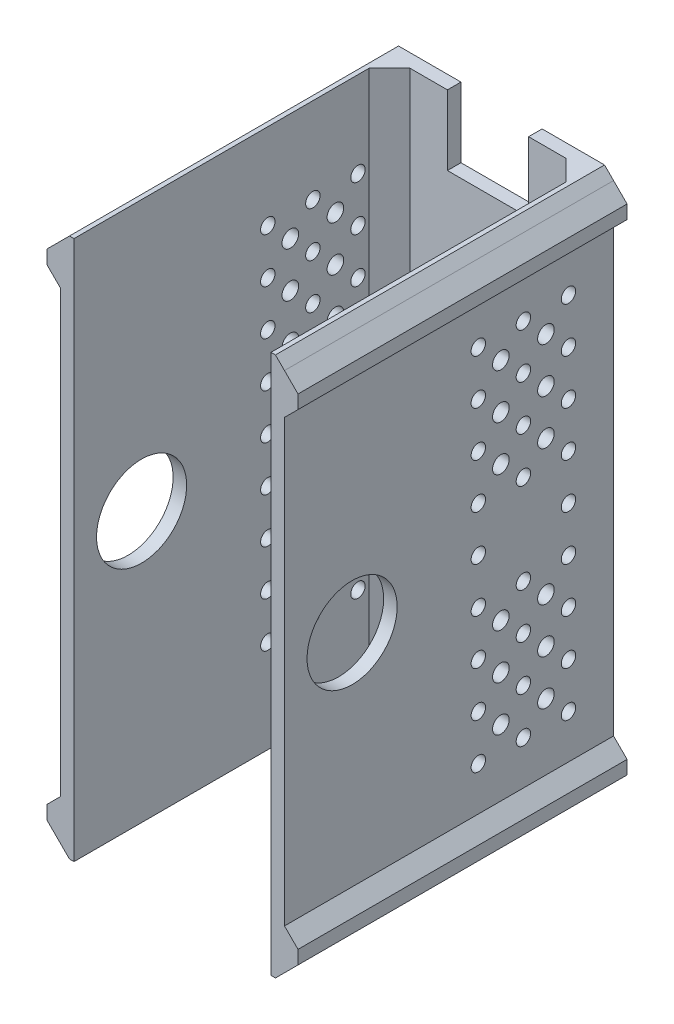
SolidWorks part; units mm, degrees
ref_plane "Front Plane" through (0, 0, 0) normal (0, 0, 1) x (1, 0, 0)
ref_plane "Top Plane" through (0, 0, 0) normal (0, 1, 0) x (1, 0, 0)
ref_plane "Right Plane" through (0, 0, 0) normal (1, 0, 0) x (0, 0, -1)
sketch "Sketch1" plane through (0, 0, 0) normal (0, 0, 1) x (1, 0, 0)
  line L0 (9, 0) -> (-9, 0)
  line L1 (-9, 0) -> (-9, -15.5)
  line L2 (-9, -15.5) -> (-24.85, -15.5)
  line L3 (-24.85, -15.5) -> (-24.85, -10.5)
  line L4 (-24.85, 44.35) -> (24.85, 44.35) construction
  line L5 (0, 88.7) -> (0, 0) construction
  line L6 (-24.85, -10.5) -> (-27.85, -10.5)
  line L7 (-27.85, -10.5) -> (-27.85, -7.5)
  line L8 (-27.85, -7.5) -> (-24.85, -7.5)
  line L9 (-24.85, -7.5) -> (-24.85, 36.35)
  line L10 (-24.85, 36.35) -> (-24.85, 41.85)
  line L11 (24.85, 41.85) -> (24.85, 46.85)
  line L12 (24.85, 36.35) -> (24.85, 41.85)
  line L13 (-24.85, 41.85) -> (-24.85, 46.85)
  line L14 (24.85, -7.5) -> (24.85, 36.35)
  line L15 (27.85, -7.5) -> (24.85, -7.5)
  line L16 (27.85, -10.5) -> (27.85, -7.5)
  line L17 (24.85, -10.5) -> (27.85, -10.5)
  line L18 (24.85, -15.5) -> (24.85, -10.5)
  line L19 (9, -15.5) -> (24.85, -15.5)
  line L20 (9, 0) -> (9, -15.5)
  line L21 (9, 88.7) -> (9, 104.2)
  line L22 (9, 104.2) -> (24.85, 104.2)
  line L23 (24.85, 104.2) -> (24.85, 99.2)
  line L24 (24.85, 99.2) -> (27.85, 99.2)
  line L25 (27.85, 99.2) -> (27.85, 96.2)
  line L26 (27.85, 96.2) -> (24.85, 96.2)
  line L27 (24.85, 96.2) -> (24.85, 52.35)
  line L28 (24.85, 52.35) -> (24.85, 46.85)
  line L29 (-24.85, 52.35) -> (-24.85, 46.85)
  line L30 (-24.85, 96.2) -> (-24.85, 52.35)
  line L31 (-27.85, 96.2) -> (-24.85, 96.2)
  line L32 (-27.85, 99.2) -> (-27.85, 96.2)
  line L33 (-24.85, 99.2) -> (-27.85, 99.2)
  line L34 (-24.85, 104.2) -> (-24.85, 99.2)
  line L35 (-9, 104.2) -> (-24.85, 104.2)
  line L36 (-9, 88.7) -> (-9, 104.2)
  line L37 (9, 88.7) -> (-9, 88.7)
  point P24 (0, 44.35)
  dimension "D1" = 9
  dimension "D2" = 15.5
  dimension "D3" = 15.85
  dimension "D4" = 59.85
  dimension "D5" = 3
  dimension "D6" = 5
extrude "Boss-Extrude1" add sketch "Sketch1" along normal blind 3
sketch "Sketch2" plane through (0, 0, 3) normal (0, 0, 1) x (1, 0, 0)
  line L0 (-24.85, 104.2) -> (-21.85, 104.2)
  line L1 (-9, 104.2) -> (-24.85, 104.2) construction
  line L2 (-24.85, 104.2) -> (-24.85, 99.2)
  line L3 (-24.85, 99.2) -> (-27.85, 99.2)
  line L4 (-27.85, 99.2) -> (-27.85, 96.2)
  line L5 (-27.85, 96.2) -> (-24.85, 96.2)
  line L6 (-24.85, 96.2) -> (-24.85, -7.5)
  line L7 (-24.85, -7.5) -> (-27.85, -7.5)
  line L8 (-27.85, -7.5) -> (-27.85, -10.5)
  line L9 (-27.85, -10.5) -> (-24.85, -10.5)
  line L10 (-24.85, -10.5) -> (-24.85, -15.5)
  line L11 (-24.85, -15.5) -> (-21.85, -15.5)
  line L12 (-21.85, 104.2) -> (-21.85, -15.5)
  line L13 (0, 88.7) -> (0, 0) construction
  line L14 (9, 88.7) -> (-9, 88.7) construction
  line L15 (21.85, 104.2) -> (21.85, -15.5)
  line L16 (24.85, -15.5) -> (21.85, -15.5)
  line L17 (24.85, -10.5) -> (24.85, -15.5)
  line L18 (27.85, -10.5) -> (24.85, -10.5)
  line L19 (27.85, -7.5) -> (27.85, -10.5)
  line L20 (24.85, -7.5) -> (27.85, -7.5)
  line L21 (24.85, 96.2) -> (24.85, -7.5)
  line L22 (27.85, 96.2) -> (24.85, 96.2)
  line L23 (27.85, 99.2) -> (27.85, 96.2)
  line L24 (24.85, 99.2) -> (27.85, 99.2)
  line L25 (24.85, 104.2) -> (24.85, 99.2)
  line L26 (24.85, 104.2) -> (21.85, 104.2)
  dimension "D1" = 3
extrude "Boss-Extrude2" add sketch "Sketch2" along normal blind 70
sketch "Sketch3" plane through (0, 0, 0) normal (0, 0, -1) x (-1, 0, 0)
  line L0 (0, 88.7) -> (0, 0) construction
  line L1 (-9, 88.7) -> (9, 88.7) construction
  line L2 (0, 44.35) -> (9, 44.35) construction
  line L3 (0, 70.85) -> (0, 17.85) construction
  circle A0 centre (9, 44.35) radius 1.65
  circle A1 centre (-4.5, 36.5558) radius 1.65
  circle A2 centre (-4.5, 52.1442) radius 1.65
  circle A3 centre (0, 44.35) radius 2.75
  circle A4 centre (0, 70.85) radius 3.5
  circle A5 centre (0, 17.85) radius 3.5
  point P14 (0, 44.35)
  point P16 (0, 44.35)
  dimension "D2" = 3.3
  dimension "D4" = 5.5
  dimension "D6" = 7
  dimension "D1" = 9
  dimension "D5" = 53
  dimension "D3" = 3
extrude "Cut-Extrude1" cut sketch "Sketch3" against normal up to surface (3 mm away) up to face at (0, 44.35, 3)
chamfer "Chamfer1" distance 4.5 angle 45 2 edges at (21.85, 44.35, 3) (-21.85, 44.35, 3)
chamfer "Chamfer2" distance 3 angle 45 8 edges at (24.85, 99.2, 36.5) (24.85, 96.2, 36.5) (24.85, -10.5, 36.5) (24.85, -7.5, 36.5) (-24.85, -7.5, 36.5) (-24.85, -10.5, 36.5) (-24.85, 99.2, 36.5) (-24.85, 96.2, 36.5)
sketch "Sketch4" plane through (-24.85, 0, 0) normal (-1, 0, 0) x (0, 0, 1)
  line L0 (73, 93.2) -> (73, -4.5) construction
  line L1 (73, 44.35) -> (58, 44.35) construction
  line L2 (10, 85.2) -> (20, 75.2) construction
  line L3 (0, 93.2) -> (10, 93.2) construction
  line L4 (0, 93.2) -> (0, 85.2) construction
  line L5 (0, 85.2) -> (10, 85.2) construction
  line L6 (10, 93.2) -> (10, 85.2) construction
  line L7 (0, 93.2) -> (10, 85.2) construction
  line L8 (0, 85.2) -> (10, 93.2) construction
  circle A0 centre (58, 44.35) radius 10
  circle A1 centre (10, 85.2) radius 1.6
  circle A2 centre (20, 85.2) radius 1.6
  circle A3 centre (30, 85.2) radius 1.6
  circle A4 centre (20, 75.2) radius 1.6
  circle A5 centre (30, 75.2) radius 1.6
  circle A6 centre (20, 65.2) radius 1.6
  circle A7 centre (30, 65.2) radius 1.6
  circle A8 centre (20, 55.2) radius 1.6
  circle A9 centre (30, 55.2) radius 1.6
  circle A10 centre (20, 45.2) radius 1.6 construction
  circle A11 centre (30, 45.2) radius 1.6
  circle A12 centre (20, 35.2) radius 1.6
  circle A13 centre (30, 35.2) radius 1.6
  circle A14 centre (20, 25.2) radius 1.6
  circle A15 centre (30, 25.2) radius 1.6
  circle A16 centre (20, 15.2) radius 1.6
  circle A17 centre (30, 15.2) radius 1.6
  circle A18 centre (20, 5.2) radius 1.6
  circle A19 centre (30, 5.2) radius 1.6
  circle A20 centre (10, 75.2) radius 1.6
  circle A21 centre (10, 65.2) radius 1.6
  circle A22 centre (10, 55.2) radius 1.6
  circle A23 centre (10, 45.2) radius 1.6
  circle A24 centre (10, 35.2) radius 1.6
  circle A25 centre (10, 25.2) radius 1.6
  circle A26 centre (10, 15.2) radius 1.6
  circle A27 centre (10, 5.2) radius 1.6
  circle A28 centre (15, 80.2) radius 1.8421
  circle A29 centre (25, 80.2) radius 1.8421
  circle A30 centre (25, 70.2) radius 1.8421
  circle A31 centre (25, 60.2) radius 1.8421
  circle A32 centre (25, 50.2) radius 1.8421 construction
  circle A33 centre (25, 40.2) radius 1.8421 construction
  circle A34 centre (25, 30.2) radius 1.8421
  circle A35 centre (25, 20.2) radius 1.8421
  circle A36 centre (25, 10.2) radius 1.8421
  circle A37 centre (15, 70.2) radius 1.8421
  circle A38 centre (15, 60.2) radius 1.8421
  circle A39 centre (15, 50.2) radius 1.8421 construction
  circle A40 centre (15, 40.2) radius 1.8421 construction
  circle A41 centre (15, 30.2) radius 1.8421
  circle A42 centre (15, 20.2) radius 1.8421
  circle A43 centre (15, 10.2) radius 1.8421
  point P11 (5, 89.2)
  dimension "D2" = 20
  dimension "D4" = 3.2
  dimension "D8" = 3.6841
  dimension "D1" = 15
  dimension "D3" = 10
  dimension "D7" = 8
  dimension "D5" = 3
  dimension "D6" = 9
  dimension "D9" = 2
  dimension "D10" = 8
extrude "Cut-Extrude2" cut sketch "Sketch4" against normal through all
chamfer "Chamfer3" distance 2 angle 45 4 edges at (24.85, -15.5, 36.5) (-24.85, -15.5, 36.5) (24.85, 104.2, 36.5) (-24.85, 104.2, 36.5)
